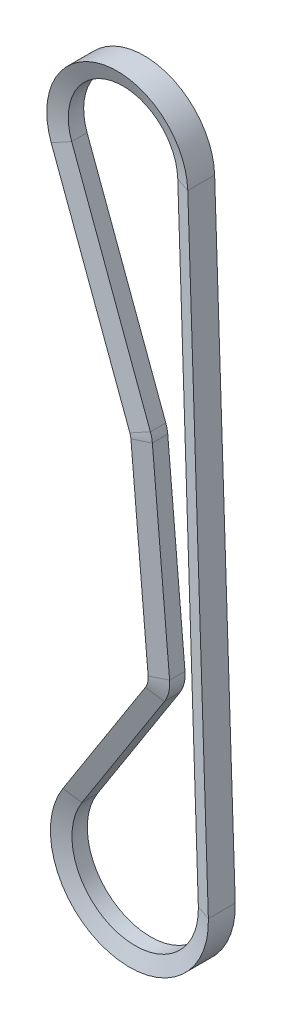
SolidWorks part; units mm, degrees
ref_plane "Front Plane" through (0, 0, 0) normal (0, 0, 1) x (1, 0, 0)
ref_plane "Top Plane" through (0, 0, 0) normal (0, 1, 0) x (1, 0, 0)
ref_plane "Right Plane" through (0, 0, 0) normal (1, 0, 0) x (0, 0, -1)
sketch "Sketch2" plane through (0, 0, 0) normal (0, 0, 1) x (1, 0, 0)
  line L0 (0, 0) -> (1, 0) construction
  line L1 (0, 0) -> (0, 1) construction
  line L12 (24.9862, 0.8291) -> (32.2818, -219.0294)
  line L14 (-19.2809, -204.8559) -> (9.9602, -159.2036)
  line L15 (10.9388, -155.2244) -> (4.8296, -85.4915)
  line L16 (4.4568, -83.8357) -> (-23.437, -8.701)
  arc A4 (32.2818, -219.0294) -> (-19.2809, -204.8559) centre (4.2972, -219.958) cw
  arc A7 (-23.437, -8.701) -> (24.9862, 0.8291) centre (0, 0) cw
  arc A8 (9.9602, -159.2036) -> (10.9388, -155.2244) centre (4.613, -155.7786) ccw
  arc A9 (4.8296, -85.4915) -> (4.4568, -83.8357) centre (-1.4962, -86.0457) ccw
ref_plane "Plane4" through (-23.437, -8.701, 0) normal (-0.348, 0.9375, 0) x (0.9375, 0.348, 0)
sketch "Sketch3" plane through (-23.437, -8.701, 0) normal (-0.348, 0.9375, 0) x (0.9375, 0.348, 0)
  line L0 (0, -4.7625) -> (0, 4.7625)
  line L1 (0, -4.7625) -> (5.588, -2.7286)
  line L2 (5.588, -2.7286) -> (5.588, 2.7286)
  line L3 (5.588, 2.7286) -> (0, 4.7625)
  line L4 (0, 0) -> (5.588, 0) construction
  dimension "D1" = 9.525
  dimension "D2" = 5.588
  dimension "D3" = 40
sweep "Sweep1" add profiles "Sketch3" path "Sketch2"
